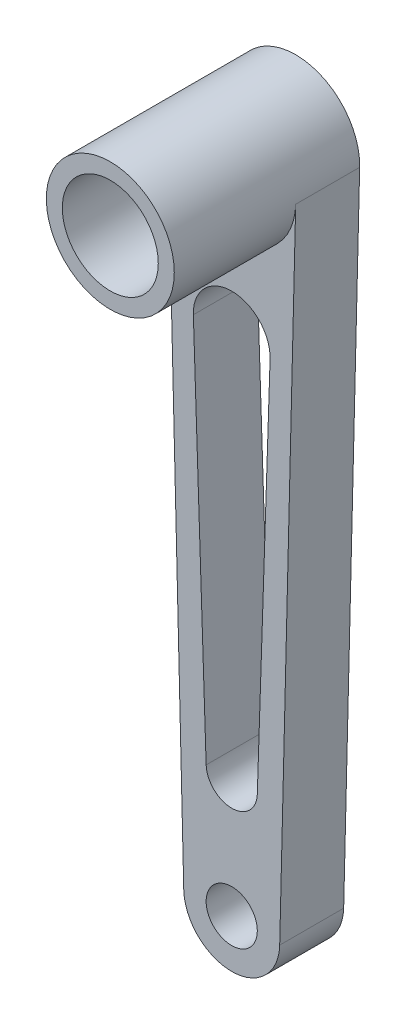
SolidWorks part; units mm, degrees
material "PEI"
ref_plane "Front Plane" through (0, 0, 0) normal (0, 0, 1) x (1, 0, 0)
ref_plane "Top Plane" through (0, 0, 0) normal (0, 1, 0) x (1, 0, 0)
ref_plane "Right Plane" through (0, 0, 0) normal (1, 0, 0) x (0, 0, -1)
sketch "Sketch1" plane through (0, 0, 0) normal (0, 0, 1) x (1, 0, 0)
  line L0 (-10.294, 11.8201) -> (-7.347, -107.9077)
  line L1 (0, -101.6) -> (0, 0) construction
  line L2 (7.347, -107.9067) -> (10.2653, 10.6574)
  line L3 (6.244, -15.7837) -> (3.867, -87.0546)
  line L4 (-6.2592, -15.3276) -> (-3.8401, -87.8596)
  circle A0 centre (0, 0) radius 10
  circle A1 centre (0, 0) radius 7.5
  circle A2 centre (0, -101.6) radius 7.5
  circle A3 centre (0, -101.6) radius 4
  circle A6 centre (0, -23) radius 6
  circle A7 centre (0, -83) radius 4
  dimension "D1" = 15
  dimension "D2" = 20
  dimension "D3" = 15
  dimension "D5" = 8
  dimension "D7" = 12
  dimension "D8" = 60
  dimension "D9" = 23
  dimension "D6" = 8
  dimension "D4" = 101.6
extrude "Boss-Extrude2" add sketch "Sketch1" along normal blind 10 contours L1 A2 L2 A0 | A2 L1 A0 L0 | A3 A2 region at (0, -11.0349, 0) region at (-0.0897, -94.3127, 0)
extrude "Boss-Extrude3" add sketch "Sketch1<6>" along normal blind 28.98 contours A0 A1 region at (-0.1196, 9.7164, 0)
sketch "Sketch1<6>" plane through (0, 0, 0) normal (0, 0, 1) x (1, 0, 0) same geometry as "Sketch1"
